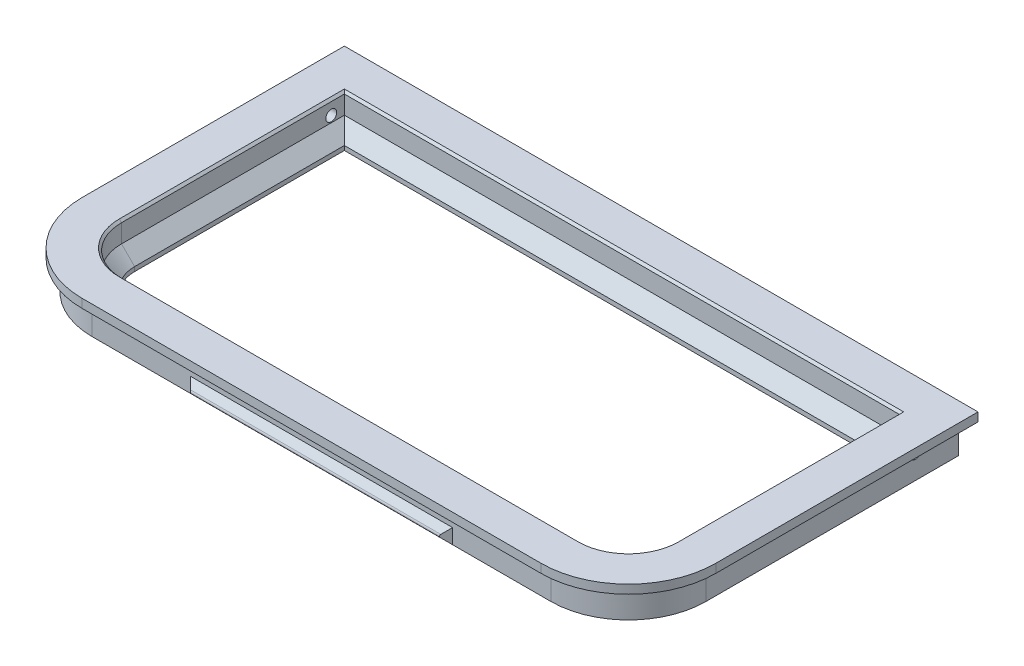
SolidWorks part; units mm, degrees
material "ПК/АБС"
ref_plane "Спереди" through (0, 0, 0) normal (0, 0, 1) x (1, 0, 0)
ref_plane "Сверху" through (0, 0, 0) normal (0, 1, 0) x (1, 0, 0)
ref_plane "Справа" through (0, 0, 0) normal (1, 0, 0) x (0, 0, -1)
sketch "Эскиз1" plane through (0, 0, 0) normal (0, 1, 0) x (1, 0, 0)
  line L1 (-72.5, -40) -> (72.5, -40)
  line L2 (-72.5, -40) -> (-72.5, 40)
  line L3 (-72.5, 40) -> (72.5, 40)
  line L4 (72.5, -40) -> (72.5, 40)
  line L5 (-72.5, -40) -> (72.5, 40) construction
  line L6 (-72.5, 40) -> (72.5, -40) construction
  point P0 (0, 0)
  dimension "D1" = 145
  dimension "D2" = 80
extrude "Бобышка-Вытянуть1" add sketch "Эскиз1" along normal blind 2
fillet "Скругление1" radius 20 2 edges at (-72.5, 1, 40) (72.5, 1, 40)
sketch "Эскиз2" plane through (0, 2, 0) normal (0, 1, 0) x (1, 0, 0)
  line L8 (-63.5, 31) -> (-63.5, -20)
  line L9 (-52.5, -31) -> (52.5, -31)
  line L10 (63.5, -20) -> (63.5, 31)
  line L11 (63.5, 31) -> (-63.5, 31)
  line L12 (-63.5, 31) -> (-63.5, -20)
  line L13 (-52.5, -31) -> (52.5, -31)
  line L14 (63.5, -20) -> (63.5, 31)
  line L15 (63.5, 31) -> (-63.5, 31)
  arc A4 (-63.5, -20) -> (-52.5, -31) centre (-52.5, -20) ccw
  arc A5 (52.5, -31) -> (63.5, -20) centre (52.5, -20) ccw
  arc A6 (-63.5, -20) -> (-52.5, -31) centre (-52.5, -20) ccw
  arc A7 (52.5, -31) -> (63.5, -20) centre (52.5, -20) ccw
  dimension "D1" = 9
extrude "Вырез-Вытянуть1" cut sketch "Эскиз2" against normal blind 2
sketch "Эскиз3" plane through (0, 0, 0) normal (0, -1, 0) x (1, 0, 0)
  line L15 (-63.5, -31) -> (-63.5, 20) construction
  line L16 (63.5, -31) -> (-63.5, -31) construction
  line L17 (63.5, 20) -> (63.5, -31) construction
  line L18 (-52.5, 31) -> (52.5, 31) construction
  line L19 (70.25, -37.75) -> (70.25, 20)
  line L20 (-70.25, -37.75) -> (70.25, -37.75)
  line L21 (-70.25, 20) -> (-70.25, -37.75)
  line L22 (52.5, 37.75) -> (-52.5, 37.75)
  line L23 (70.25, -37.75) -> (70.25, 20)
  line L24 (-70.25, -37.75) -> (70.25, -37.75)
  line L25 (-70.25, 20) -> (-70.25, -37.75)
  line L26 (52.5, 37.75) -> (-52.5, 37.75)
  line L27 (-63.5, -31) -> (-63.5, 20)
  line L28 (63.5, -31) -> (-63.5, -31)
  line L29 (63.5, 20) -> (63.5, -31)
  line L30 (-52.5, 31) -> (52.5, 31)
  arc A6 (-52.5, 31) -> (-63.5, 20) centre (-52.5, 20) ccw construction
  arc A7 (63.5, 20) -> (52.5, 31) centre (52.5, 20) ccw construction
  arc A8 (70.25, 20) -> (52.5, 37.75) centre (52.5, 20) ccw
  arc A9 (-52.5, 37.75) -> (-70.25, 20) centre (-52.5, 20) ccw
  arc A10 (70.25, 20) -> (52.5, 37.75) centre (52.5, 20) ccw
  arc A11 (-52.5, 37.75) -> (-70.25, 20) centre (-52.5, 20) ccw
  arc A12 (-52.5, 31) -> (-63.5, 20) centre (-52.5, 20) ccw
  arc A13 (63.5, 20) -> (52.5, 31) centre (52.5, 20) ccw
  dimension "D1" = 6.75
extrude "Бобышка-Вытянуть2" add sketch "Эскиз3" along normal blind 2
sketch "Эскиз5" plane through (0, 0, 0) normal (1, 0, 0) x (0, 0, -1)
  line L0 (-20, 0) -> (40, 0) construction
  line L7 (37.75, -2) -> (31, -2)
  line L9 (31, -2) -> (31, -6.7)
  line L10 (31, -6.7) -> (37.75, -6.7)
  line L11 (37.75, -6.7) -> (39.45, -5)
  line L12 (39.45, -5) -> (37.75, -3.3)
  line L13 (37.75, -3.3) -> (37.75, -2)
  line L14 (31, -2) -> (31, 2) construction
  line L15 (31, -2) -> (31, 2) construction
  line L16 (-31, -2) -> (-31, 2) construction
  line L17 (-31, -2) -> (-31, 2) construction
  line L18 (-31, -2) -> (-31, -6.7)
  line L19 (-31, -6.7) -> (-37.75, -6.7)
  line L20 (-37.75, -6.7) -> (-39.45, -5)
  line L21 (-39.45, -5) -> (-37.75, -3.3)
  line L22 (-37.75, -3.3) -> (-37.75, -2)
  line L23 (-37.75, -2) -> (-31, -2)
  dimension "D1" = 5
  dimension "D2" = 1.7
  dimension "D4" = 1.7
extrude "Бобышка-Вытянуть4" add sketch "Эскиз5" along normal mid plane 30
sketch "Эскиз6" plane through (0, 0, 0) normal (1, 0, 0) x (0, 0, -1)
  line L6 (-39.45, -5) -> (-37.75, -6.7)
  line L7 (-37.75, -6.7) -> (-31, -6.7)
  line L8 (-31, -6.7) -> (-31, -2)
  line L9 (-31, -2) -> (-37.75, -2)
  line L10 (-37.75, -2) -> (-37.75, -3.3)
  line L11 (-37.75, -3.3) -> (-39.45, -5)
  line L12 (-39.45, -5) -> (-37.75, -6.7)
  line L13 (-37.75, -6.7) -> (-31, -6.7)
  line L14 (-31, -6.7) -> (-31, -2)
  line L15 (-31, -2) -> (-37.75, -2)
  line L16 (-37.75, -2) -> (-37.75, -3.3)
  line L17 (-37.75, -3.3) -> (-39.45, -5)
  dimension "D1" = 0
extrude "Бобышка-Вытянуть5" add sketch "Эскиз6" along normal mid plane 60
fillet "Скругление2" radius 0.5 2 edges at (0, -5, 39.45) (0, -5, -39.45)
sketch "Эскиз7" plane through (0, -2, 0) normal (0, -1, 0) x (1, 0, 0)
  line L8 (-52.5, 31) -> (-30, 31)
  line L9 (-30, 31) -> (-30, 37.75)
  line L10 (-30, 37.75) -> (-52.5, 37.75)
  line L11 (-70.25, 20) -> (-70.25, -37.75)
  line L12 (-70.25, -37.75) -> (-15, -37.75)
  line L13 (-15, -37.75) -> (-15, -31)
  line L14 (-15, -31) -> (-63.5, -31)
  line L15 (-63.5, -31) -> (-63.5, 20)
  line L16 (-52.5, 31) -> (-30, 31)
  line L17 (-30, 31) -> (-30, 37.75)
  line L18 (-30, 37.75) -> (-52.5, 37.75)
  line L19 (-70.25, 20) -> (-70.25, -37.75)
  line L20 (-70.25, -37.75) -> (-15, -37.75)
  line L21 (-15, -37.75) -> (-15, -31)
  line L22 (-15, -31) -> (-63.5, -31)
  line L23 (-63.5, -31) -> (-63.5, 20)
  line L24 (30, 37.75) -> (30, 31)
  line L25 (30, 31) -> (52.5, 31)
  line L26 (63.5, 20) -> (63.5, -31)
  line L27 (63.5, -31) -> (15, -31)
  line L28 (15, -31) -> (15, -37.75)
  line L29 (15, -37.75) -> (70.25, -37.75)
  line L30 (70.25, -37.75) -> (70.25, 20)
  line L31 (52.5, 37.75) -> (30, 37.75)
  line L32 (30, 37.75) -> (30, 31)
  line L33 (30, 31) -> (52.5, 31)
  line L34 (63.5, 20) -> (63.5, -31)
  line L35 (63.5, -31) -> (15, -31)
  line L36 (15, -31) -> (15, -37.75)
  line L37 (15, -37.75) -> (70.25, -37.75)
  line L38 (70.25, -37.75) -> (70.25, 20)
  line L39 (52.5, 37.75) -> (30, 37.75)
  arc A2 (-52.5, 37.75) -> (-70.25, 20) centre (-52.5, 20) ccw
  arc A3 (-52.5, 31) -> (-63.5, 20) centre (-52.5, 20) ccw
  arc A4 (-52.5, 37.75) -> (-70.25, 20) centre (-52.5, 20) ccw
  arc A5 (-52.5, 31) -> (-63.5, 20) centre (-52.5, 20) ccw
  arc A6 (63.5, 20) -> (52.5, 31) centre (52.5, 20) ccw
  arc A7 (70.25, 20) -> (52.5, 37.75) centre (52.5, 20) ccw
  arc A8 (63.5, 20) -> (52.5, 31) centre (52.5, 20) ccw
  arc A9 (70.25, 20) -> (52.5, 37.75) centre (52.5, 20) ccw
  dimension "D1" = 0
  dimension "D2" = 0
extrude "Бобышка-Вытянуть6" add sketch "Эскиз7" along normal up to surface (4.7 mm away) up to face at (0, -6.7, 34.375)
sketch "Эскиз10" plane through (0, -6.7, 0) normal (0, -1, 0) x (1, 0, 0)
  line L14 (-63.5, 20) -> (-63.5, -31) construction
  line L15 (63.5, -31) -> (-63.5, -31) construction
  line L16 (63.5, -31) -> (63.5, 20) construction
  line L17 (52.5, 31) -> (-52.5, 31) construction
  line L18 (60.5, -28) -> (60.5, 20)
  line L19 (-60.5, -28) -> (60.5, -28)
  line L20 (-60.5, 20) -> (-60.5, -28)
  line L21 (52.5, 28) -> (-52.5, 28)
  line L22 (60.5, -28) -> (60.5, 20)
  line L23 (-60.5, -28) -> (60.5, -28)
  line L24 (-60.5, 20) -> (-60.5, -28)
  line L25 (52.5, 28) -> (-52.5, 28)
  line L26 (-63.5, 20) -> (-63.5, -31)
  line L27 (63.5, -31) -> (-63.5, -31)
  line L28 (63.5, -31) -> (63.5, 20)
  line L29 (52.5, 31) -> (-52.5, 31)
  arc A7 (-52.5, 31) -> (-63.5, 20) centre (-52.5, 20) ccw construction
  arc A8 (63.5, 20) -> (52.5, 31) centre (52.5, 20) ccw construction
  arc A9 (60.5, 20) -> (52.5, 28) centre (52.5, 20) ccw
  arc A10 (-52.5, 28) -> (-60.5, 20) centre (-52.5, 20) ccw
  arc A11 (60.5, 20) -> (52.5, 28) centre (52.5, 20) ccw
  arc A12 (-52.5, 28) -> (-60.5, 20) centre (-52.5, 20) ccw
  arc A13 (-52.5, 31) -> (-63.5, 20) centre (-52.5, 20) ccw
  arc A14 (63.5, 20) -> (52.5, 31) centre (52.5, 20) ccw
  dimension "D1" = 3
extrude "Бобышка-Вытянуть9" add sketch "Эскиз10" against normal blind 1
chamfer "Фаска2" distance 3 angle 45 6 edges at (0, -5.7, -31) (63.5, -5.7, -5.5) (-63.5, -5.7, -5.5) (60.2782, -5.7, 27.7782) (-60.2782, -5.7, 27.7782) (0, -5.7, 31)
sketch "Эскиз11" plane through (70.25, 0, 0) normal (1, 0, 0) x (0, 0, -1)
  line L0 (40, 2) -> (40, 0) construction
  line L1 (-20, 2) -> (40, 2) construction
  circle A0 centre (28, -1.25) radius 1.25
  dimension "D1" = 2.5
  dimension "D2" = 12
  dimension "D3" = 3.25
extrude "Вырез-Вытянуть2" cut sketch "Эскиз11" against normal through all
chamfer "Фаска3" distance 0.5 angle 45 6 edges at (63.5, 2, -5.5) (60.2782, 2, 27.7782) (0, 2, 31) (-60.2782, 2, 27.7782) (-63.5, 2, -5.5) (0, 2, -31)
sketch "Эскиз12" plane through (0, 0, 0) normal (0, -1, 0) x (1, 0, 0)
  line L0 (-30, 37.75) -> (-28, 39.75)
  line L1 (-28, 39.75) -> (-30, 39.75)
  line L2 (-30, 39.75) -> (-30, 37.75)
  line L3 (30, 37.75) -> (30, 39.75)
  line L4 (30, 39.75) -> (28, 39.75)
  line L5 (28, 39.75) -> (30, 37.75)
  line L6 (-15, -37.75) -> (-15, -39.75)
  line L7 (-15, -39.75) -> (-13, -39.75)
  line L8 (-13, -39.75) -> (-15, -37.75)
  line L9 (15, -37.75) -> (13, -39.75)
  line L10 (13, -39.75) -> (15, -39.75)
  line L11 (15, -39.75) -> (15, -37.75)
  dimension "D1" = 2
extrude "Вырез-Вытянуть3" cut sketch "Эскиз12" along normal through all
